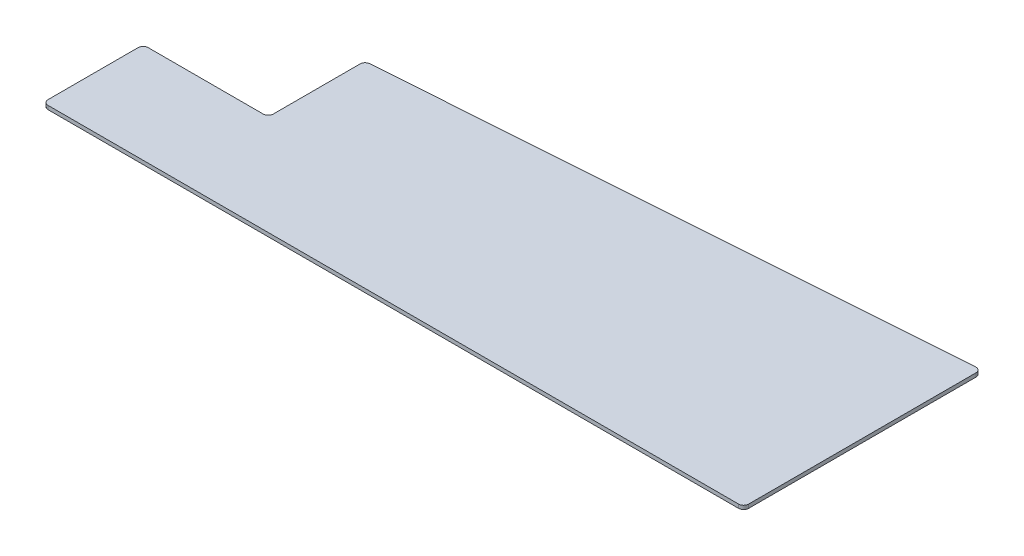
SolidWorks part; units mm, degrees
material "6061 Alloy"
ref_plane "Front Plane" through (0, 0, 0) normal (0, 0, 1) x (1, 0, 0)
ref_plane "Top Plane" through (0, 0, 0) normal (0, 1, 0) x (1, 0, 0)
ref_plane "Right Plane" through (0, 0, 0) normal (1, 0, 0) x (0, 0, -1)
sketch "Sketch1" plane through (0, 0, 0) normal (0, 1, 0) x (1, 0, 0)
  line L0 (0, 0) -> (280, 0)
  line L1 (0, 40) -> (0, 0)
  line L3 (280, 95) -> (280, 0)
  line L4 (50, 78.5721) -> (50, 40)
  line L5 (50, 40) -> (0, 40)
  line L7 (50, 78.5721) -> (280, 95)
  dimension "D1" = 40
  dimension "D2" = 280
  dimension "D3" = 95
  dimension "D4" = 50
  dimension "D5" = 38.5721
sheet metal parameters "Sheet-Metal1" thickness 1.5 parameters "D1"=0.7366
base flange "Vertical Wall" sketch "Sketch1" thickness 1.5 reverse thickness direction no parameters "D1"=0.7366
fillet "Fillet1" radius 2 6 edges at (50, -0.75, -40) (280, -0.75, 0) (280, -0.75, -95) (0, -0.75, 0) (0, -0.75, -40) (50, -0.75, -78.5721)
flat pattern "Flat-Pattern1" [suppressed]
sketch "Bend-Lines1" plane through (0, 0, 0) normal (0, 1, 0) x (1, 0, 0)
  point P0 (93.1821, -1.7566)
  point P1 (103.1821, -1.7566)
  point P2 (239.2046, -1.7566)
  point P3 (249.2046, -1.7566)
  point P4 (357.0941, -1.02)
  point P5 (377.0941, -1.02)
  point P6 (-76.9773, -1.02)
  point P7 (-56.9773, -1.02)
  point P8 (281.047, 0)
  point P9 (281.047, 94.9716)
  point P10 (-0.9887, 60.0001)
  point P11 (-0.9887, 0)
sketch3d "Bounding-Box1" [suppressed]
  line L0 (383.1845, -15.1242, 0) -> (-75.2412, -40.9331, 0) construction
  line L1 (376.6789, 100.4309, 0) -> (-81.7468, 74.622, 0) construction
  line L2 (383.1845, -15.1242, 0) -> (376.6789, 100.4309, 0) construction
  line L3 (-75.2412, -40.9331, 0) -> (-81.7468, 74.622, 0) construction
